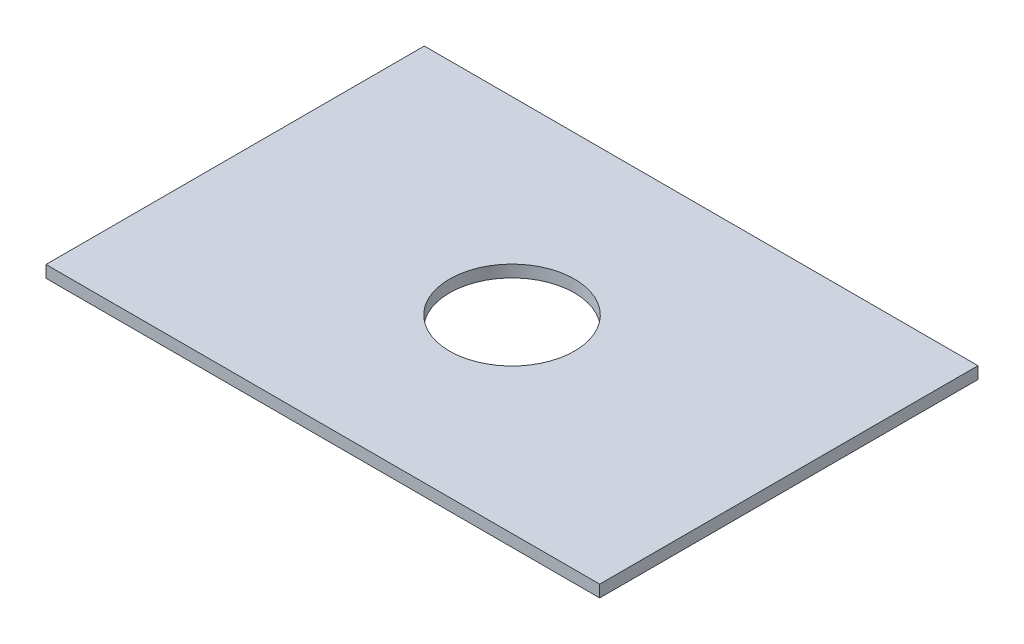
SolidWorks part; units mm, degrees
material "Oak"
ref_plane "Front Plane" through (0, 0, 0) normal (0, 0, 1) x (1, 0, 0)
ref_plane "Top Plane" through (0, 0, 0) normal (0, 1, 0) x (1, 0, 0)
ref_plane "Right Plane" through (0, 0, 0) normal (1, 0, 0) x (0, 0, -1)
sketch "Sketch1" plane through (0, 0, 0) normal (0, 1, 0) x (1, 0, 0)
  line L1 (0, 0) -> (146.35, 0)
  line L2 (0, 0) -> (0, 100)
  line L3 (0, 100) -> (146.35, 100)
  line L4 (146.35, 0) -> (146.35, 100)
  dimension "D1" = 146.35
  dimension "D2" = 100
extrude "Boss-Extrude1" add sketch "Sketch1" along normal blind 3.175
sketch "Sketch2" plane through (0, 3.175, 0) normal (0, 1, 0) x (1, 0, 0)
  line L0 (73.175, 100) -> (73.175, 0) construction
  line L1 (146.35, 100) -> (0, 100) construction
  line L2 (0, 0) -> (146.35, 0) construction
  line L3 (0, 50) -> (146.35, 50) construction
  line L4 (0, 100) -> (0, 0) construction
  line L5 (146.35, 0) -> (146.35, 100) construction
  circle A0 centre (73.175, 50) radius 16.51
  dimension "D1" = 33.02
extrude "Cut-Extrude1" cut sketch "Sketch2" against normal blind 10
